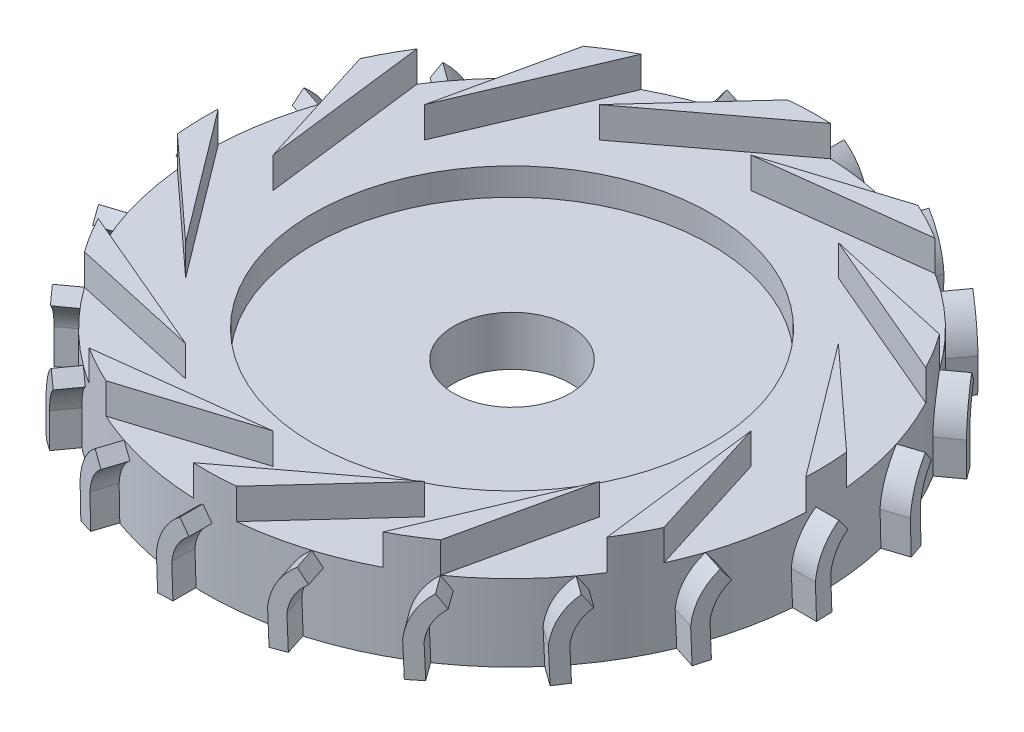
SolidWorks part; units mm, degrees
ref_plane "Front Plane" through (0, 0, 0) normal (0, 0, 1) x (1, 0, 0)
ref_plane "Top Plane" through (0, 0, 0) normal (0, 1, 0) x (1, 0, 0)
ref_plane "Right Plane" through (0, 0, 0) normal (1, 0, 0) x (0, 0, -1)
sketch "Sketch1" plane through (0, 0, 0) normal (1, 0, 0) x (0, 0, -1)
  line L0 (0, 26.2631) -> (0, -1.0485) construction
  line L1 (0, -1.0485) -> (-50.8, -1.0485)
  line L2 (-50.8, -1.0485) -> (-50.8, 11.6515)
  line L3 (-33.0001, 11.6515) -> (-50.8, 11.6515)
  line L4 (-33.0001, 11.6515) -> (-33.0001, 7.1515)
  line L5 (-33.0001, 7.1515) -> (0, 7.1515)
  line L6 (0, 7.1515) -> (0, -1.0485)
  dimension "D1" = 33.0001
  dimension "D2" = 50.8
  dimension "D3" = 4.5
  dimension "D4" = 12.7
revolve "Revolve1" add sketch "Sketch1" angle 360 about L0
sketch "Sketch2" plane through (0, 11.6515, 0) normal (0, 1, 0) x (1, 0, 0)
  line L8 (0, 39.6001) -> (19.9397, 39.6001) construction
  line L9 (0, 39.6001) -> (21.0453, 46.2356)
  line L10 (0, 39.6001) -> (27.1669, 42.9255)
  circle A0 centre (0, 0) radius 50.8 construction
  arc A1 (21.0453, 46.2356) -> (27.1669, 42.9255) centre (0, 0) cw
  circle A5 centre (0, 0) radius 33.0001 construction
  circle A7 centre (0, 0) radius 39.6001 construction
  point P9 (-2.4416, -40.4611)
  dimension "D1" = 66.0001
  dimension "D2" = 79.2001
  dimension "D3" = 17.5
extrude "Boss-Extrude1" add sketch "Sketch2" along normal blind 5.08
pattern_circular "CirPattern1" count 12 over 360 about axis through (0, 11.6515, 0) along (0, 1, 0) of "Boss-Extrude1"
ref_plane "Plane1" through (0, 0, 49.53) normal (0, 0, 1) x (1, 0, 0)
sketch "Sketch3" plane through (0, 0, 49.53) normal (0, 0, 1) x (1, 0, 0)
  line L0 (0, 0) -> (0, 9.7621) construction
  line L1 (0, -55) -> (0, 55) construction
  line L5 (-21.0453, 11.6515) -> (0, 11.6515) construction
  line L6 (-50.8, -1.0485) -> (50.8, -1.0485) construction
  line L7 (-4.3287, 4.6923) -> (-4.1287, -1.0485)
  line L10 (-1.7845, 4.6163) -> (-1.5903, -0.9601)
  line L11 (1.0729, 9.6084) -> (-0.4363, 11.6515)
  line L12 (-4.1287, -1.0485) -> (-1.5903, -0.9601)
  arc A4 (-0.4363, 11.6515) -> (-4.3287, 4.6923) centre (5.3144, 3.8668) ccw
  arc A5 (1.0729, 9.6084) -> (-1.7845, 4.6163) centre (5.3144, 3.8668) ccw
  dimension "D1" = 2.54
extrude "Boss-Extrude2" add sketch "Sketch3" along normal blind 5.08 and the other way blind 0.254
pattern_circular "CirPattern16" count 20 over 360 about axis through (0, -1.0485, 0) along (0, 1, 0) of "Boss-Extrude2"
sketch "Sketch4" plane through (0, 7.1515, 0) normal (0, 1, 0) x (1, 0, 0)
  circle A0 centre (0, 0) radius 9.652
  dimension "D1" = 19.304
extrude "Cut-Extrude1" cut sketch "Sketch4" against normal up to next
sketch "Sketch5" plane through (0, -1.0485, 0) normal (0, -1, 0) x (-1, 0, 0)
  circle A0 centre (0, 0) radius 38.1
  dimension "D1" = 76.2
extrude "Cut-Extrude2" cut sketch "Sketch5" against normal blind 7.62
sketch "Sketch6" plane through (0, 6.5715, 0) normal (0, -1, 0) x (1, 0, 0)
  circle A0 centre (0, 0) radius 19.05
  circle A1 centre (0, 0) radius 9.652 construction
  circle A2 centre (0, 0) radius 9.652
  dimension "D1" = 38.1
extrude "Boss-Extrude3" add sketch "Sketch6" along normal up to surface (7.62 mm away) up to face at (0, -1.0485, -38.1)
